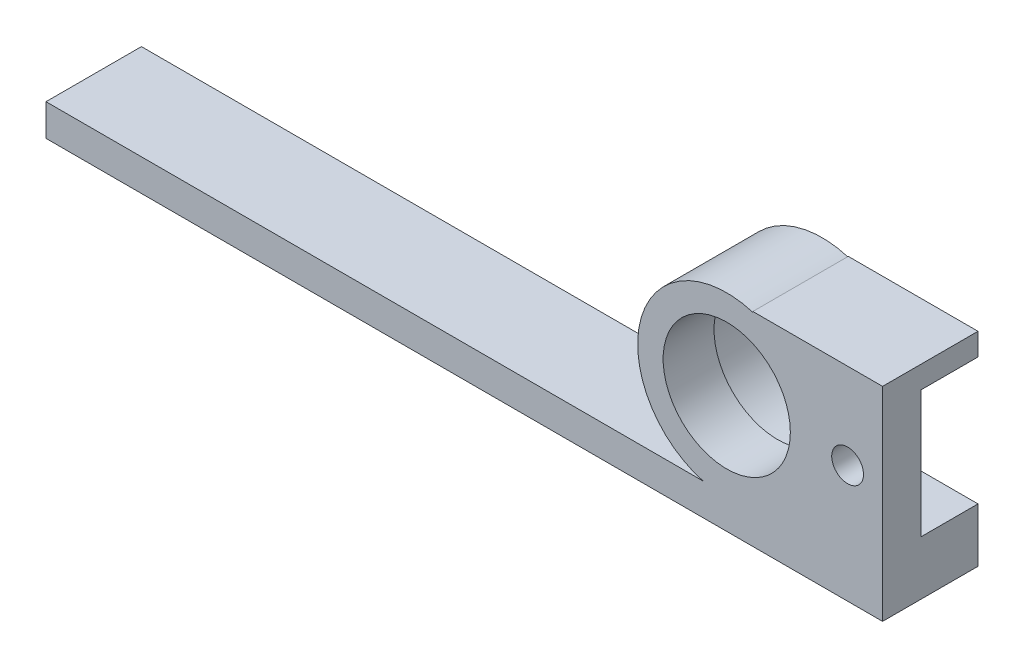
SolidWorks part; units mm, degrees
ref_plane "前视基准面" through (0, 0, 0) normal (0, 0, 1) x (1, 0, 0)
ref_plane "上视基准面" through (0, 0, 0) normal (0, 1, 0) x (1, 0, 0)
ref_plane "右视基准面" through (0, 0, 0) normal (1, 0, 0) x (0, 0, -1)
sketch "草图1" plane through (0, 0, 0) normal (0, 0, 1) x (1, 0, 0)
  line L1 (20, -10) -> (-20, -10)
  line L2 (20, -10) -> (20, 10)
  line L3 (20, 10) -> (-20, 10)
  line L4 (-20, -10) -> (-20, 10)
  line L5 (20, -10) -> (-20, 10) construction
  line L6 (20, 10) -> (-20, -10) construction
  point P0 (0, 0)
  dimension "D1" = 40
  dimension "D2" = 20
extrude "凸台-拉伸1" add sketch "草图1" along normal blind 6
sketch "草图2" plane through (0, 0, 6) normal (0, 0, 1) x (1, 0, 0)
  line L0 (20, -10) -> (20, 10) construction
  circle A0 centre (10, 0) radius 2.5
  circle A1 centre (-1, 0) radius 2.5
  circle A2 centre (-12, 0) radius 2.5
  dimension "D1" = 10
  dimension "D2" = 5
  dimension "D3" = 3
extrude "切除-拉伸1" cut sketch "草图2" against normal through all
sketch "草图3" plane through (0, 0, 6) normal (0, 0, 1) x (1, 0, 0)
  line L0 (20, 13.5) -> (20, 10)
  line L1 (20, -13.5) -> (-26.894, -13.5)
  line L3 (20, 13.5) -> (-26.894, 13.5)
  line L4 (-20, 10) -> (-20, -10)
  line L5 (-20, -10) -> (20, -10)
  line L6 (20, -10) -> (20, 10)
  line L7 (20, 10) -> (-20, 10)
  line L8 (-20, 10) -> (-20, -10)
  line L9 (-20, -10) -> (20, -10)
  line L10 (20, -10) -> (20, 10)
  line L11 (20, 10) -> (-20, 10)
  line L12 (-26.894, -13.5) -> (-26.894, 13.5)
  line L13 (20, -10.0394) -> (-26.894, 13.5) construction
  line L14 (20, 10.0394) -> (-26.894, -13.5) construction
  line L15 (20, -10) -> (20, -13.5)
  circle A0 centre (-31, 0) radius 11
  circle A1 centre (-31, 0) radius 14
  point P2 (0, 0)
  line M10 (-20, 10) -> (-20, -10)
  line M11 (-20, -10) -> (20, -10)
  line M13 (20, 10) -> (-20, 10)
  dimension "D3" = 22
  dimension "D4" = 28
  dimension "D2" = 3.5
  dimension "D1" = 0
extrude "凸台-拉伸2" add sketch "草图3" against normal blind 15 contours L3 A1 L1 L12 A0 | A1 L1 L15 M11 M10 | L1 A1 L8 A0 L12 | L8 A1 L3 L12 A0 | L8 A1 | A1 L0 L3 M10 M13 region at (-1.9449, 11.7771, 6) region at (-1.9449, -11.7771, 6) region at (-23.0173, 9.0328, 6) region at (-27.2274, 11.7946, 6) region at (-18.7882, 0, 6) region at (-23.0173, -9.0328, 6)
sketch "草图5" plane through (0, 0, 6) normal (0, 0, 1) x (1, 0, 0)
  circle A0 centre (-31, 0) radius 10
  circle A1 centre (-31, 0) radius 11 construction
  circle A2 centre (-31, 0) radius 11
  dimension "D1" = 20
extrude "凸台-拉伸3" add sketch "草图5" against normal blind 8
sketch "草图6" plane through (0, 0, 6) normal (0, 0, 1) x (1, 0, 0)
  circle A0 centre (-31, 0) radius 8.5
  circle A1 centre (-31, 0) radius 10 construction
  circle A2 centre (-31, 0) radius 10
  dimension "D1" = 17
sketch "草图8" plane through (0, 0, 6) normal (0, 0, 1) x (1, 0, 0)
  line L0 (20, -13.5) -> (20, 13.5) construction
  line L1 (20, -13.5) -> (-26.894, -13.5) construction
  line L2 (20, 13.5) -> (-26.894, 13.5) construction
  line L3 (20, -13.5) -> (20, 13.5)
  line L4 (20, -13.5) -> (-26.894, -13.5)
  line L5 (20, 13.5) -> (-26.894, 13.5)
  line L6 (-45, -14) -> (-26.894, -13.5)
  line L7 (-45, -14) -> (-239, -14)
  line L8 (-45, -14) -> (-45, 14)
  line L9 (-45, 14) -> (-239, 14)
  line L10 (-239, -14) -> (-239, 14)
  line L11 (-45, -14) -> (-239, 14) construction
  line L12 (-45, 14) -> (-239, -14) construction
  line L13 (-45, 14) -> (-26.894, 13.3843)
  line L14 (-12, 0) -> (-31, 0)
  arc A0 (-26.894, 13.3843) -> (-26.894, -13.3843) centre (-31, 0) ccw construction
  arc A1 (-26.894, 13.3843) -> (-26.894, -13.3843) centre (-31, 0) ccw
  point P6 (-142, 0)
  dimension "D1" = 28
  dimension "D2" = 194
  dimension "D3" = 14
sketch "草图9" plane through (0, -13.5, 0) normal (0, -1, 0) x (1, 0, 0)
  circle A0 centre (10.5344, 0) radius 5.2388
sketch "草图10" plane through (20, 0, 0) normal (1, 0, 0) x (0, 0, -1)
  line L1 (9, -13.5) -> (-6, -13.5)
  line L2 (9, -13.5) -> (9, -18.5)
  line L3 (9, -18.5) -> (-6, -18.5)
  line L4 (-6, -13.5) -> (-6, -18.5)
  dimension "D1" = 5
extrude "凸台-拉伸4" add sketch "草图10" against normal blind 500
sketch "草图11" plane through (0, 0, -9) normal (0, 0, -1) x (-1, 0, 0)
  line L1 (22.0371, -11.3638) -> (33.5283, -11.3638)
  line L2 (22.0371, -11.3638) -> (22.0371, -16.4864)
  line L3 (22.0371, -16.4864) -> (33.5283, -16.4864)
  line L4 (33.5283, -11.3638) -> (33.5283, -16.4864)
extrude "凸台-拉伸5" add sketch "草图11" against normal through all
sketch "草图12" plane through (0, 0, 6) normal (0, 0, 1) x (1, 0, 0)
  line L0 (-12, 0) -> (-1, 0) construction
  line L1 (-6.5, 0) -> (-6.5, 13.5) construction
  line L2 (20, 13.5) -> (-26.894, 13.5) construction
  line L4 (-6.5, 13.5) -> (20, 13.5)
  line L5 (-6.5, 13.5) -> (-6.5, -18.5)
  line L6 (-6.5, -18.5) -> (20, -18.5)
  line L7 (20, 13.5) -> (20, -18.5)
extrude "切除-拉伸2" cut sketch "草图12" against normal through all
sketch "草图13" plane through (0, -18.5, 0) normal (0, -1, 0) x (1, 0, 0)
  line L0 (-138.0156, 6) -> (-138.0156, -9.0491)
  line L1 (-480, 6) -> (-6.5, 6) construction
  line L2 (-138.0156, 230.7091) -> (-138.0156, -139.2909) construction
sketch "草图14" plane through (0, -18.5, 0) normal (0, -1, 0) x (1, 0, 0)
  line L1 (-138.0156, -9.0491) -> (-494.0275, -9.0491)
  line L2 (-138.0156, -9.0491) -> (-138.0156, 12.8124)
  line L3 (-138.0156, 12.8124) -> (-494.0275, 12.8124)
  line L4 (-494.0275, -9.0491) -> (-494.0275, 12.8124)
extrude "切除-拉伸3" cut sketch "草图14" against normal through all
